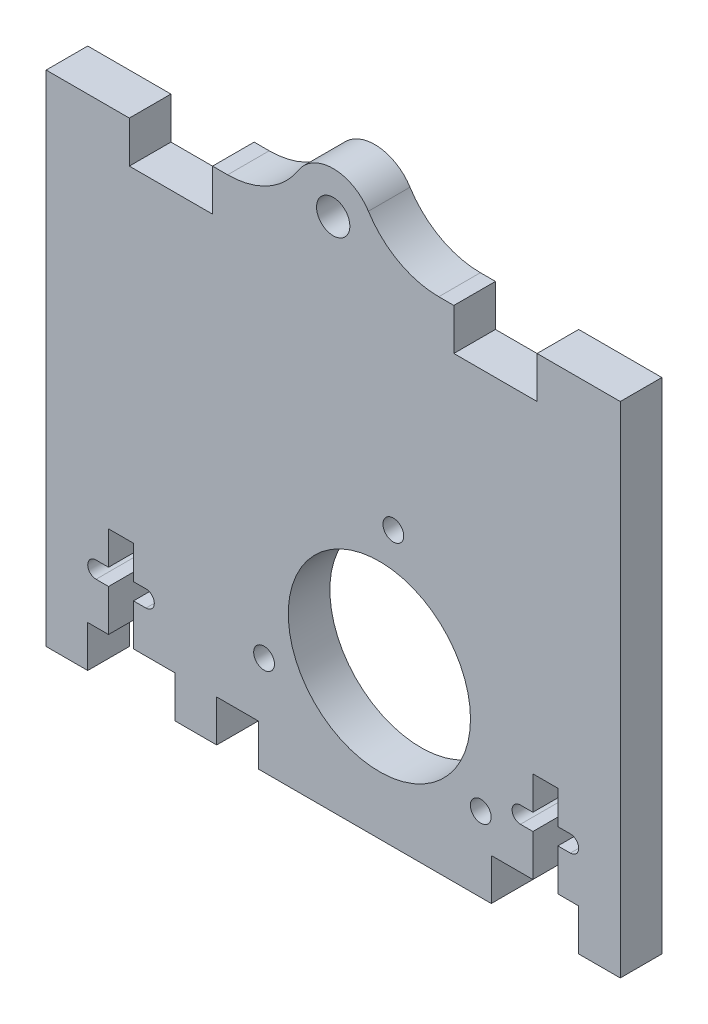
SolidWorks part; units mm, degrees
ref_plane "Front Plane" through (0, 0, 0) normal (0, 0, 1) x (1, 0, 0)
ref_plane "Top Plane" through (0, 0, 0) normal (0, 1, 0) x (1, 0, 0)
ref_plane "Right Plane" through (0, 0, 0) normal (1, 0, 0) x (0, 0, -1)
sketch "Sketch8" plane through (0, 0, 0) normal (0, 0, 1) x (1, 0, 0)
  line L0 (-29.414, -24.275) -> (39.586, -24.275)
  line L1 (-29.414, -24.275) -> (-29.414, 30.725)
  line L2 (-29.414, 30.725) -> (-0.414, 30.725)
  line L3 (39.586, -24.275) -> (39.586, -9.275)
  line L4 (33.586, -18.275) -> (27.586, -18.275) construction
  line L5 (39.586, -24.275) -> (24.5628, -24.275)
  line L6 (32.086, -24.275) -> (29.086, -24.275)
  line L7 (32.086, -24.275) -> (32.086, -13.275)
  line L8 (32.086, -13.275) -> (29.086, -13.275)
  line L9 (29.086, -24.275) -> (29.086, -13.275)
  line L10 (33.586, -19.275) -> (27.586, -19.275)
  line L11 (33.586, -17.275) -> (27.586, -17.275)
  line L12 (30.586, -13.275) -> (30.586, -18.275) construction
  line L13 (30.586, -18.275) -> (30.586, -24.275) construction
  line L14 (-18.914, -24.275) -> (-21.914, -24.275)
  line L15 (-18.914, -24.275) -> (-18.914, -13.275)
  line L16 (-18.914, -13.275) -> (-21.914, -13.275)
  line L17 (-21.914, -24.275) -> (-21.914, -13.275)
  line L18 (-20.414, -13.275) -> (-20.414, -18.275) construction
  line L19 (-20.414, -18.275) -> (-20.414, -24.275) construction
  line L20 (-17.414, -18.275) -> (-23.414, -18.275) construction
  line L21 (-17.414, -19.275) -> (-23.414, -19.275)
  line L22 (-17.414, -17.275) -> (-23.414, -17.275)
  line L23 (-17.414, 24.725) -> (-23.414, 24.725) construction
  line L24 (-17.414, 25.725) -> (-23.414, 25.725)
  line L25 (-17.414, 23.725) -> (-23.414, 23.725)
  line L26 (-20.414, 24.725) -> (-20.414, 30.725) construction
  line L27 (-20.414, 19.725) -> (-20.414, 24.725) construction
  line L28 (-21.914, 30.725) -> (-21.914, 19.725)
  line L29 (-18.914, 19.725) -> (-21.914, 19.725)
  line L30 (-18.914, 30.725) -> (-18.914, 19.725)
  line L31 (-18.914, 30.725) -> (-21.914, 30.725)
  line L32 (21.586, -1011.325) -> (21.586, 48988.675) construction
  line L33 (26.586, -1018.275) -> (26.586, 48981.725) construction
  line L34 (34.586, -1018.275) -> (34.586, 48981.725) construction
  line L35 (-24.414, -1018.275) -> (-24.414, 48981.725) construction
  circle A0 centre (-8.586, 1.275) radius 7
  circle A1 centre (10.636, -11.325) radius 10.95
  circle A2 centre (-8.586, 13.775) radius 1.5
  circle A3 centre (3.914, 1.275) radius 1.5
  circle A4 centre (-8.586, -11.225) radius 1.5
  circle A5 centre (-21.086, 1.275) radius 1.5
  arc A6 (-0.414, 30.725) -> (39.586, -9.275) centre (-0.414, -9.275) cw
  arc A7 (33.586, -19.275) -> (33.586, -17.275) centre (33.586, -18.275) ccw
  arc A8 (27.586, -17.275) -> (27.586, -19.275) centre (27.586, -18.275) ccw
  arc A9 (-17.414, -19.275) -> (-17.414, -17.275) centre (-17.414, -18.275) ccw
  arc A10 (-23.414, -17.275) -> (-23.414, -19.275) centre (-23.414, -18.275) ccw
  arc A11 (-17.414, 25.725) -> (-17.414, 23.725) centre (-17.414, 24.725) cw
  arc A12 (-23.414, 23.725) -> (-23.414, 25.725) centre (-23.414, 24.725) cw
  point P25 (30.586, -18.275)
  point P41 (-20.414, -18.275)
  point P51 (-20.414, 24.725)
  point P66 (26.586, -18.275)
  point P69 (34.586, -18.275)
  point P72 (-24.414, -18.275)
  dimension "D1" = 14
  dimension "D2" = 40
  dimension "D11" = 21.9
  dimension "D3" = 3
  dimension "D4" = 11
  dimension "D5" = 2
  dimension "D6" = 8
  dimension "D7" = 5
  dimension "D8" = 55
  dimension "D9" = 5
  dimension "D10" = 5
  dimension "D12" = 5
extrude "Boss-Extrude1" add sketch "Sketch8" along normal blind 5 contours L25 A12 L24 L28 L2 L1 L0 L17 L21 A10 L22 L16 L15 A9 L9 L10 A8 L11 L8 L7 A7 L3 A6 L30 A11 L29 A5 A4 A3 A2 region at (2.446, 3.3638, 0)
sketch "Sketch9" plane through (0, 0, 0) normal (0, 0, -1) x (-1, 0, 0)
  line L0 (18.914, -24.275) -> (-29.086, -24.275) construction
  line L1 (-24.086, -24.275) -> (3.914, -24.275)
  line L2 (-24.086, -24.275) -> (-24.086, -29.275)
  line L3 (-24.086, -29.275) -> (3.914, -29.275)
  line L4 (13.914, -24.275) -> (13.914, -29.275)
  line L5 (-29.086, -24.275) -> (-29.086, -19.275) construction
  line L6 (18.914, -24.275) -> (18.914, -19.275) construction
  line L7 (8.914, -29.275) -> (13.914, -29.275)
  line L8 (-39.586, -24.275) -> (-34.586, -24.275)
  line L9 (-39.586, -24.275) -> (-39.586, -29.275)
  line L11 (-39.586, -24.275) -> (-39.586, -9.275) construction
  line L12 (29.414, 30.725) -> (-39.586, 30.725)
  line L13 (29.414, 30.725) -> (29.414, 11.7466)
  line L14 (29.414, 11.7466) -> (10.7623, 11.7466)
  line L15 (-39.586, 30.725) -> (-39.586, 11.7466)
  line L16 (6.4097, 11.7466) -> (-17.7432, 11.7466)
  line L17 (-39.586, -29.275) -> (-34.586, -29.275)
  line L18 (-34.586, -24.275) -> (-34.586, -29.275)
  line L19 (-39.586, 11.7466) -> (-39.586, -2.995)
  line L20 (29.414, -24.275) -> (24.414, -24.275)
  line L21 (29.414, -24.275) -> (29.414, -29.275)
  line L22 (29.414, -29.275) -> (24.414, -29.275)
  line L23 (24.414, -24.275) -> (24.414, -29.275)
  line L24 (-26.161, -2.995) -> (-17.7432, -2.995)
  line L25 (-17.7432, 11.7466) -> (-17.7432, -2.995)
  line L26 (-39.586, -9.275) -> (-26.161, -9.275)
  line L27 (-39.586, -9.275) -> (-39.586, -2.995)
  line L29 (-26.161, -9.275) -> (-26.161, -2.995)
  line L30 (8.914, -24.275) -> (8.914, -29.275)
  line L32 (3.914, -24.275) -> (3.914, -29.275)
  line L33 (8.914, -24.275) -> (13.914, -24.275)
  arc A0 (10.7623, 11.7466) -> (6.4097, 11.7466) centre (8.586, 13.775) ccw
  circle A1 centre (-10.636, -11.325) radius 10.95 construction
  dimension "D1" = 5
  dimension "D2" = 5
  dimension "D3" = 5
  dimension "D10" = 5
  dimension "D4" = 5
extrude "Boss-Extrude2" add sketch "Sketch9" against normal blind 5
sketch "Sketch10" plane through (0, 0, 0) normal (0, 0, -1) x (-1, 0, 0)
  arc A0 (0.2424, -12.5751) -> (-7.4428, -0.8509) centre (8.586, 1.275) ccw
  arc A1 (0.2424, -12.5751) -> (-7.4428, -0.8509) centre (-10.636, -11.325) ccw
extrude "Boss-Extrude3" add sketch "Sketch10" against normal blind 5
sketch "Sketch11" plane through (0, 0, 5) normal (0, 0, 1) x (1, 0, 0)
  line L0 (-29.414, 30.725) -> (39.586, 30.725) construction
  line L1 (-19.414, 30.725) -> (-9.414, 30.725)
  line L2 (-19.414, 30.725) -> (-19.414, 25.725)
  line L3 (-19.414, 25.725) -> (-9.414, 25.725)
  line L4 (-9.414, 30.725) -> (-9.414, 25.725)
  line L5 (-29.414, -29.275) -> (-29.414, 30.725) construction
  line L6 (29.586, 30.725) -> (19.586, 30.725)
  line L7 (29.586, 30.725) -> (29.586, 25.725)
  line L8 (29.586, 25.725) -> (19.586, 25.725)
  line L9 (19.586, 30.725) -> (19.586, 25.725)
  line L10 (39.586, -29.275) -> (39.586, 30.725) construction
  line L11 (-9.414, 32.725) -> (19.586, 32.725) construction
  circle A0 centre (5.086, 32.725) radius 2
  circle A1 centre (5.086, 32.725) radius 5
  line M2 (39.586, 30.725) -> (-29.414, 30.725)
  dimension "D5" = 4
  dimension "D1" = 5
  dimension "D2" = 10
  dimension "D3" = 10
  dimension "D4" = 10
extrude "Boss-Extrude4" add sketch "Sketch11" against normal blind 5
extrude "Cut-Extrude1" cut sketch "Sketch11<2>" against normal blind 5 contours L4 L2 L3 M2 | L9 L8 L7 M2 region at (24.586, 28.225, 5) region at (-14.414, 28.225, 5)
sketch "Sketch11<2>" plane through (0, 0, 5) normal (0, 0, 1) x (1, 0, 0) same geometry as "Sketch11"
fillet "Fillet1" radius 10 2 edges at (9.6685, 30.725, 2.5) (0.5034, 30.725, 2.5)
fillet "Fillet2" [suppressed] radius 10
sketch "Sketch12" plane through (0, 0, 5) normal (0, 0, 1) x (1, 0, 0)
  circle A0 centre (22.8181, -20.2942) radius 4.1778 construction
  circle A1 centre (22.8181, -20.2942) radius 1.25
  circle A2 centre (-3.2227, -17.3904) radius 1.25
  circle A3 centre (12.3125, 3.7096) radius 1.25
  point P4 (10.636, -11.325)
  dimension "D1" = 2.5
extrude "Cut-Extrude2" cut sketch "Sketch12" against normal blind 10
